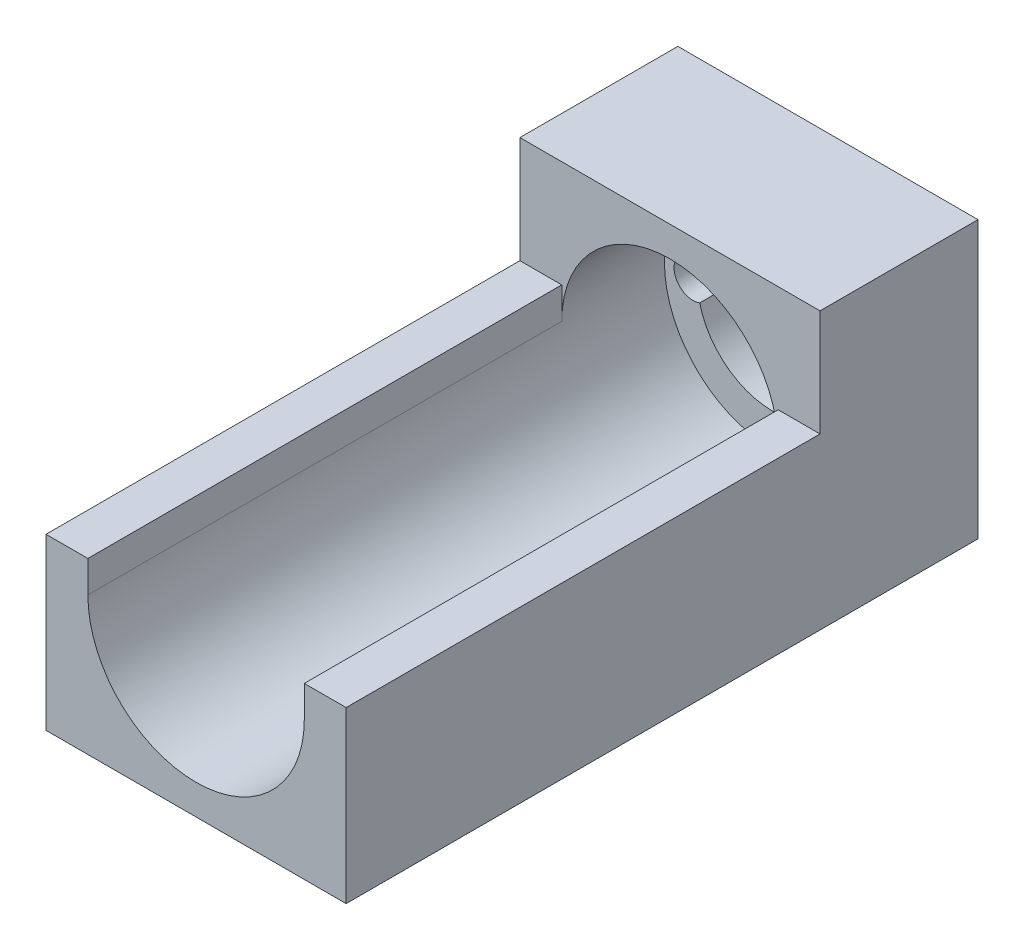
SolidWorks part; units mm, degrees
ref_plane "Alzado" through (0, 0, 0) normal (0, 0, 1) x (1, 0, 0)
ref_plane "Planta" through (0, 0, 0) normal (0, 1, 0) x (1, 0, 0)
ref_plane "Vista lateral" through (0, 0, 0) normal (1, 0, 0) x (0, 0, -1)
sketch "Croquis1" plane through (0, 0, 0) normal (0, 0, 1) x (1, 0, 0)
  line L0 (0, 8.3596) -> (0, -1.3417) construction
  line L1 (9, 0.75) -> (-9, 0.75)
  line L2 (0, 0.75) -> (0, -0.75)
  line L3 (9, -0.75) -> (-9, -0.75)
  line L4 (-9, 0.75) -> (-9, -0.75)
  line L5 (-12.48, 10.7299) -> (-12.48, -4.9079) construction
  line L6 (9, 0.75) -> (9, -0.75)
  line L7 (0, 0) -> (-17.6562, 0) construction
  circle A0 centre (-10.08, 0) radius 2.4
  circle A1 centre (-10.08, 0) radius 0.9
  circle A2 centre (10.08, 0) radius 0.9
  circle A3 centre (10.08, 0) radius 2.4
  circle A4 centre (0, 0) radius 13.7
  point P9 (0, 0)
  dimension "D1" = 1.8
  dimension "D4" = 4.8
  dimension "D6" = 27.4
  dimension "D2" = 1.5
  dimension "D3" = 9
  dimension "D5" = 12.48
extrude "Saliente-Extruir1" add sketch "Croquis1" along normal blind 5 contours A4 L1 A3 L3 A0 region at (-13.3125, 0, 0)
sketch "Croquis2" plane through (0, 0, 5) normal (0, 0, 1) x (1, 0, 0)
  circle A0 centre (0, 0) radius 9.5
  dimension "D1" = 19
extrude "Cortar-Extruir1" cut sketch "Croquis2" against normal blind 3.5
sketch "Croquis3" plane through (0, 0, 1.5) normal (0, 0, 1) x (1, 0, 0)
  circle A0 centre (0, 0) radius 6.8
  dimension "D1" = 13.6
extrude "Cortar-Extruir2" cut sketch "Croquis3" against normal blind 3
sketch "Croquis4" plane through (0, 0, 0) normal (0, 0, -1) x (-1, 0, 0)
  circle A0 centre (0, 0) radius 13.7 construction
  circle A1 centre (0, 0) radius 13.7
  circle A2 centre (0, 0) radius 6.65
  dimension "D1" = 13.3
extrude "Saliente-Extruir2" add sketch "Croquis4" along normal blind 2
sketch "Croquis5" plane through (0, 0, 5) normal (0, 0, 1) x (1, 0, 0)
  circle A0 centre (-10.08, 0) radius 1.25
  circle A1 centre (10.08, 0) radius 1.25
  dimension "D1" = 2.5
  dimension "D2" = 2.5
extrude "Cortar-Extruir3" cut sketch "Croquis5" against normal through all
sketch "Croquis6" plane through (0, 0, -2) normal (0, 0, -1) x (-1, 0, 0)
  line L1 (-19, -17.5) -> (19, -17.5)
  line L2 (-19, -17.5) -> (-19, 17.5)
  line L3 (-19, 17.5) -> (19, 17.5)
  line L4 (19, -17.5) -> (19, 17.5)
  line L5 (-19, -17.5) -> (19, 17.5) construction
  line L6 (-19, 17.5) -> (19, -17.5) construction
  circle A0 centre (0, 0) radius 13.7 construction
  circle A1 centre (0, 0) radius 13.7
  point P0 (0, 0)
  dimension "D1" = 35
  dimension "D2" = 38
extrude "Saliente-Extruir3" add sketch "Croquis6" against normal blind 20 separate body
sketch "Croquis8" plane through (0, 0, 18) normal (0, 0, 1) x (1, 0, 0)
  line L0 (-13.7, 0) -> (-13.7, 4)
  line L1 (-13.7, 4) -> (19, 4)
  line L2 (13.7, 0) -> (13.7, 4)
  line L3 (13.7, 4) -> (-19, 4)
  line L4 (-19, 17.5) -> (-19, -17.5)
  line L5 (19, 17.5) -> (-19, 17.5)
  line L6 (19, -17.5) -> (19, 17.5)
  line L7 (-19, -17.5) -> (19, -17.5)
  line L8 (-19, 17.5) -> (-19, 4)
  line L10 (19, 4) -> (19, 17.5)
  line L11 (-19, -17.5) -> (19, -17.5)
  line L12 (19, 17.5) -> (19, -17.5) construction
  line L13 (27.021, 0) -> (-27.7174, 0) construction
  circle A0 centre (0, 0) radius 13.7 construction
  circle A1 centre (0, 0) radius 13.7 construction
  arc A2 (-13.7, 0) -> (13.7, 0) centre (0, 0) ccw
  point P13 (0, 0)
  circle M15 centre (0, 0) radius 13.7
  line M16 (-19, 17.5) -> (-19, -17.5)
  line M17 (-19, -17.5) -> (19, -17.5)
  line M18 (19, -17.5) -> (19, 17.5)
  dimension "D2" = 4
  dimension "D3" = 4
  dimension "D1" = 0
extrude "Saliente-Extruir5" add sketch "Croquis8" along normal blind 60 contours L13 M18 M15 M16 M17 | L13 L0 L3 M16 | L13 L1 L2 M18 region at (-16.35, 2, 18) region at (0, -14.1184, 18) region at (16.35, 2, 18)
